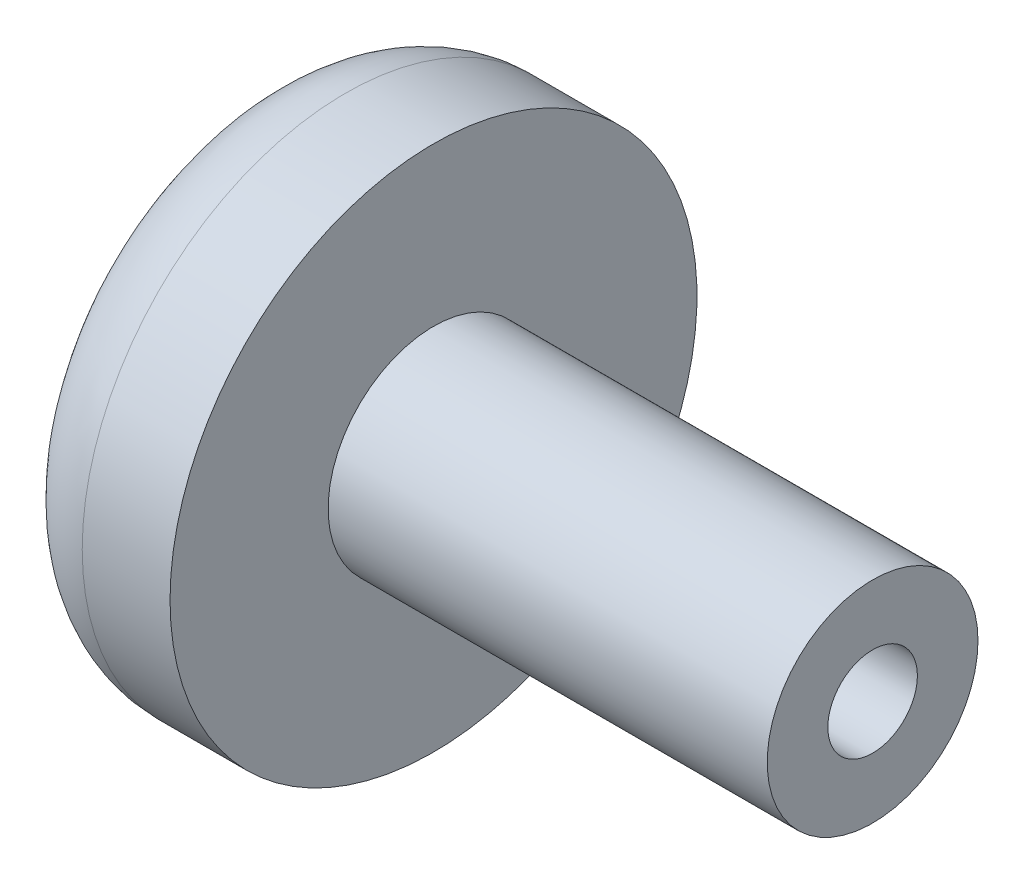
SolidWorks part; units mm, degrees
ref_plane "Front Plane" through (0, 0, 0) normal (0, 0, 1) x (1, 0, 0)
ref_plane "Top Plane" through (0, 0, 0) normal (0, 1, 0) x (1, 0, 0)
ref_plane "Right Plane" through (0, 0, 0) normal (1, 0, 0) x (0, 0, -1)
sketch "Sketch1" plane through (0, 0, 0) normal (1, 0, 0) x (0, 0, -1)
  circle A0 centre (0, 0) radius 7.62
  circle A1 centre (0, 0) radius 3.2385
  dimension "D1" = 15.24
  dimension "D2" = 6.477
extrude "Boss-Extrude1" add sketch "Sketch1" along normal blind 31.75
sketch "Sketch2" plane through (0, 0, 0) normal (0, 0, 1) x (1, 0, 0)
  line L0 (15.875, 7.62) -> (15.875, -7.62) construction
  line L1 (31.75, 7.62) -> (0, 7.62) construction
  line L2 (0, -7.62) -> (31.75, -7.62) construction
  circle A0 centre (15.875, 0) radius 1.651
  dimension "D1" = 3.302
extrude "Cut-Extrude1" cut sketch "Sketch2" against normal blind 11.684
sketch "Sketch4" plane through (0, 0, 0) normal (-1, 0, 0) x (0, 0, 1)
  circle A0 centre (0, 0) radius 19.05
  dimension "D1" = 38.1
extrude "Boss-Extrude2" add sketch "Sketch4" along normal blind 12.7
fillet "Fillet1" radius 6.35 1 edges at (-12.7, 0, 19.05)
ref_plane "Plane1" through (0, 0, -5.08) normal (0, 0, 1) x (1, 0, 0)
sketch "Sketch5" plane through (0, 0, -5.08) normal (0, 0, 1) x (1, 0, 0)
  circle A0 centre (15.875, 0) radius 1.651 construction
  circle A1 centre (15.875, 0) radius 1.651
thread "Thread1" pitch 0.7 method cut profile "Thread Profile1" start angle 0, offset 6.08, length 10, pitch 0.7, diameter 3.302
ref_plane "Plane2" through (17.526, 0, -11.16) normal (0, -1, 0) x (1, 0, 0)
sketch "Thread Profile1" plane through (17.526, 0, -11.16) normal (0, -1, 0) x (1, 0, 0)
  line L0 (0, 0) -> (0, 0.7) construction
  line L1 (0, 0) -> (0.3789, 0.2187)
  line L2 (0.3789, 0.2187) -> (0.3789, 0.3062)
  line L3 (0.3789, 0.3062) -> (0, 0.525)
  line L4 (0.3789, 0.2625) -> (0, 0.2625) construction
  line L11 (0, 0) -> (0, 0.525)
  point P2 (0, 0)
  dimension "Pitch" = 0.7
  dimension "Profile_Angle" = 60
  dimension "Profile_Land" = 0.0875
  dimension "Profile_Height" = 0.3789
